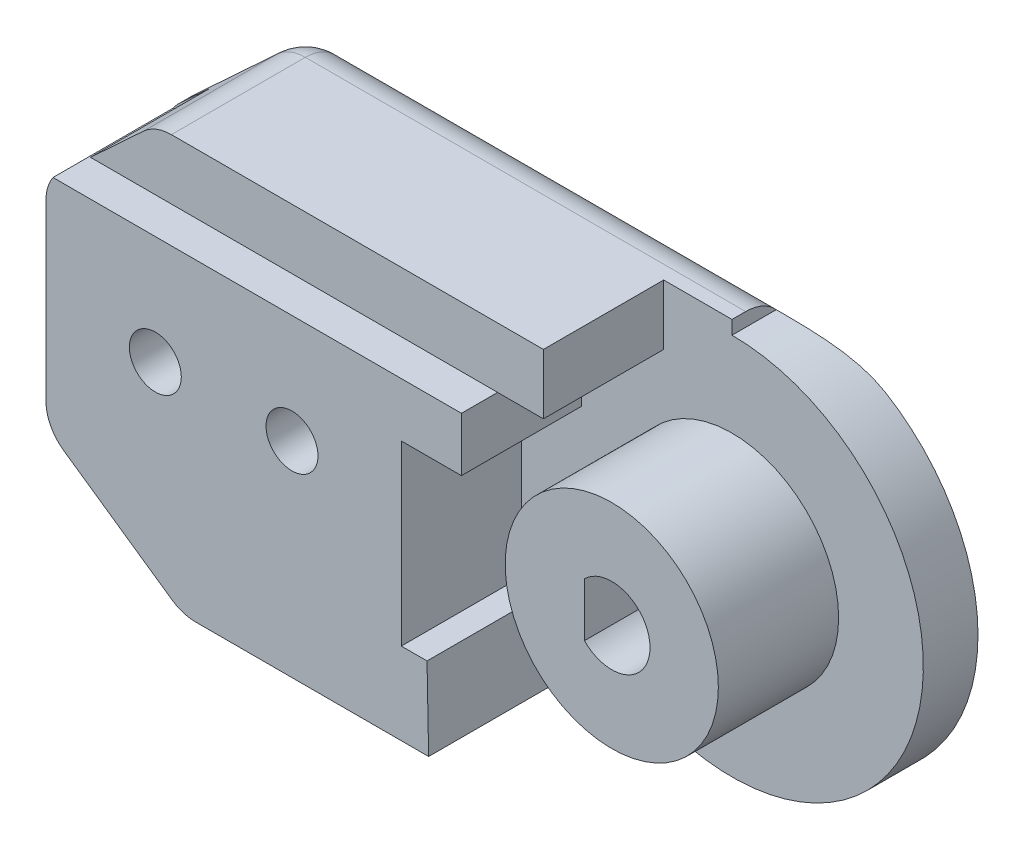
SolidWorks part; units mm, degrees
ref_plane "Front Plane" through (0, 0, 0) normal (0, 0, 1) x (1, 0, 0)
ref_plane "Top Plane" through (0, 0, 0) normal (0, 1, 0) x (1, 0, 0)
ref_plane "Right Plane" through (0, 0, 0) normal (1, 0, 0) x (0, 0, -1)
sketch "Sketch2" plane through (0, 0, 0) normal (0, 0, 1) x (1, 0, 0)
  line L1 (-2.5, 7.5) -> (-16.7, 7.5)
  line L2 (-20.7, 3.7934) -> (-20.7, -4.0316)
  line L3 (-15.7, -7.5) -> (-6.7, -7.5)
  line L4 (-6.7, -7.5) -> (-4.2, -5.6)
  line L5 (-2.5, 7.5) -> (0, 7.5)
  line L7 (0, 7) -> (0, 7.5)
  line L8 (-20.7, 3.7934) -> (-16.7, 7.5)
  line L9 (-20.7, -4.0316) -> (-15.7, -7.5)
  arc A1 (-4.2, -5.6) -> (7, 0) centre (0, 0) ccw
  arc A2 (7, 0) -> (0, 7) centre (0, 0) ccw
  dimension "D1" = 7
  dimension "D2" = 4
  dimension "D3" = 5
  dimension "D4" = 7.5
  dimension "D5" = 15
  dimension "D7" = 2.5
  dimension "D8" = 14
extrude "Boss-Extrude1" add sketch "Sketch2" along normal blind 2 contours A1 A2 L7 L5 L1 L8 L2 L9 L3 L4
sketch "Sketch4" plane through (0, 0, 2) normal (0, 0, 1) x (1, 0, 0)
  line L7 (-15.7, -7.5) -> (-6.7, -7.5)
  line L8 (-6.7, -7.5) -> (-6.7591, -4.5)
  line L9 (-6.7591, -4.5) -> (-7.7, -4.5)
  line L10 (-16.7, 7.5) -> (-2.5, 7.5)
  line L13 (-5.5, 2) -> (-5.5, 5.3)
  line L14 (-5.5, 5.3) -> (-2.5, 5.3)
  line L21 (-20.7, -4.0316) -> (-15.7, -7.5)
  line L24 (-16.7, 7.5) -> (-20.7, 3.7934)
  line L25 (-20.7, -4.0316) -> (-20.7, 3.7934)
  line L26 (-7.7, 2) -> (-5.5, 2)
  line L29 (-7.7, 2) -> (-7.7, -4.5)
  line L30 (-2.5, 7.5) -> (-2.5, 5.3)
  point P2 (-5.5, 3.65)
  dimension "D1" = 13
  dimension "D2" = 2.5
  dimension "D3" = 3
  dimension "D4" = 3
  dimension "D5" = 3.3
  dimension "D6" = 2.2
extrude "Boss-Extrude2" add sketch "Sketch4" along normal blind 8
ref_point "Point1"
sketch "Sketch22" plane through (0, 0, 2) normal (0, 0, 1) x (1, 0, 0)
  line L0 (0, 5.3) -> (-14, 5.3) construction
  line L1 (0, 4) -> (-14, 4) construction
  line L2 (-14, 4) -> (-14, 5.3) construction
  circle A0 centre (0, 0) radius 5.3 construction
  circle A1 centre (0, 0) radius 4 construction
  dimension "D1" = 14
  dimension "D2" = 10.6
  dimension "D3" = 8
sketch "Sketch24" plane through (0, 0, 2) normal (0, 0, 1) x (1, 0, 0)
  circle A0 centre (0, 0) radius 3.9
  dimension "D1" = 7.8
extrude "Boss-Extrude5" add sketch "Sketch24" along normal blind 4.4
sketch "Sketch29" plane through (-5.5, 0, 0) normal (1, 0, 0) x (0, 0, -1)
  line L0 (-1.9279, 3.9758) -> (-10, 3.9758) construction
  line L1 (-10, 2) -> (-10, 5.3) construction
sketch "Sketch30" plane through (-5.5, 0, 0) normal (1, 0, 0) x (0, 0, -1)
  line L0 (-6.4086, 3.9758) -> (-6.4086, 5.3)
  line L1 (-6.4086, 3.9758) -> (-2, 3.9758)
  line L2 (-6.4086, 5.3) -> (-2, 5.3)
  line L3 (-2, 3.9758) -> (-2, 5.3)
  line L6 (-2, 2) -> (-2, 5.3) construction
  line L7 (-10, 5.3) -> (-2, 5.3) construction
  dimension "D1" = 4.4086
extrude "Cut-Extrude12" cut sketch "Sketch30" against normal blind 16
ref_plane "Plane1" through (0, 0, 10) normal (0, 0, 1) x (1, 0, 0)
sketch "Sketch8" plane through (0, 0, 2) normal (0, 0, 1) x (1, 0, 0)
  circle A1 centre (0, 0) radius 3.8
  circle A2 centre (0, 0) radius 2.5
sketch "Sketch28" plane through (0, 0, 6.4) normal (0, 0, 1) x (1, 0, 0)
  line L0 (-1, 0.9798) -> (-1, -0.9798)
  arc A0 (-1, -0.9798) -> (-1, 0.9798) centre (0, 0) ccw
  dimension "D1" = 1
  dimension "D2" = 1.4
extrude "Cut-Extrude11" cut sketch "Sketch28" against normal through all
sketch "Sketch33" plane through (0, 0, 10) normal (0, 0, 1) x (1, 0, 0)
  line L0 (-7, 2) -> (-0.5657, -5.1566) construction
  line L2 (-8.2591, -4.5) -> (-2.6001, 3.0469) construction
  dimension "D1" = 1.5
  dimension "D2" = 1.5
fillet "Fillet1" radius 1.5 9 edges at (-11.2, -7.5, 0) (-8.35, 7.5, 0) (-18.7, 5.6467, 0) (-18.2, -5.7658, 0) (-20.7, -0.1191, 0) (-15.7, -7.5, 5) (-20.7, -4.0316, 5) (-20.7, 3.7934, 5) (-16.7, 7.5, 5)
sketch "Sketch34" plane through (0, 2, 0) normal (0, -1, 0) x (1, 0, 0)
  line L4 (-7.7, 10) -> (-5.5, 10) construction
  line L5 (-6.2, 10.75) -> (-7.7, 10.75)
  line L6 (-6.2, 10.75) -> (-6.2, 9.25)
  line L7 (-6.2, 9.25) -> (-7.7, 9.25)
  line L8 (-7.7, 10.75) -> (-7.7, 9.25)
  line L9 (-6.2, 10.75) -> (-7.7, 9.25) construction
  line L10 (-6.2, 9.25) -> (-7.7, 10.75) construction
  line L12 (-7.7, 10) -> (-7.7, 2) construction
  point P0 (-6.95, 10)
  dimension "D1" = 1.5
  dimension "D2" = 1.5
extrude "Cut-Extrude13" cut sketch "Sketch34" along direction (0.6686, -0.7436, 0) on the side against the normal blind 8
sketch "Sketch35" plane through (0, -4.5, 0) normal (0, 1, 0) x (1, 0, 0)
  circle A0 centre (-8.2591, -10) radius 0.75
sketch "Sketch36" plane through (0, 0, 10) normal (0, 0, 1) x (1, 0, 0)
  line L0 (-20.7, 3.1384) -> (-20.7, -3.2466) construction
  line L1 (-12.6449, 7.5) -> (-16.1119, 7.5) construction
  line L2 (-7.7, -4.5) -> (-7.7, 2) construction
  circle A0 centre (-11.7, 0) radius 0.95
  circle A1 centre (-16.7, 0) radius 0.95
  dimension "D1" = 4
  dimension "D2" = 5
  dimension "D5" = 1.9
  dimension "D3" = 4
  dimension "D4" = 7.5
extrude "Cut-Extrude15" cut sketch "Sketch36" against normal blind 8
sketch "Sketch37" plane through (0, 0, 0) normal (0, 0, -1) x (-1, 0, 0)
  circle A0 centre (11.7, 0) radius 2
  circle A1 centre (16.7, 0) radius 2
  dimension "D1" = 4
extrude "Cut-Extrude16" cut sketch "Sketch37" against normal blind 4.5
sketch "Sketch38" plane through (0, 0, 10) normal (0, 0, 1) x (1, 0, 0)
  line L0 (-5.5, 5.3) -> (-2.5, 5.3)
  line L1 (-5.5, 5.3) -> (-5.5, 6.55)
  line L2 (-2.5, 5.3) -> (-2.5, 6.55)
  line L3 (-5.5, 6.55) -> (-2.5, 6.55)
  dimension "D1" = 1.25
extrude "Cut-Extrude17" cut sketch "Sketch38" against normal blind 3.6
ref_plane "Plane2" through (0, 0, 6.4) normal (0, 0, 1) x (1, 0, 0)
split "Split1" trim tools "Plane2" bodies to split 129 resulting bodies 130 131
delete or keep bodies "Body-Delete/Keep 1" type delete bodies bodies 130
